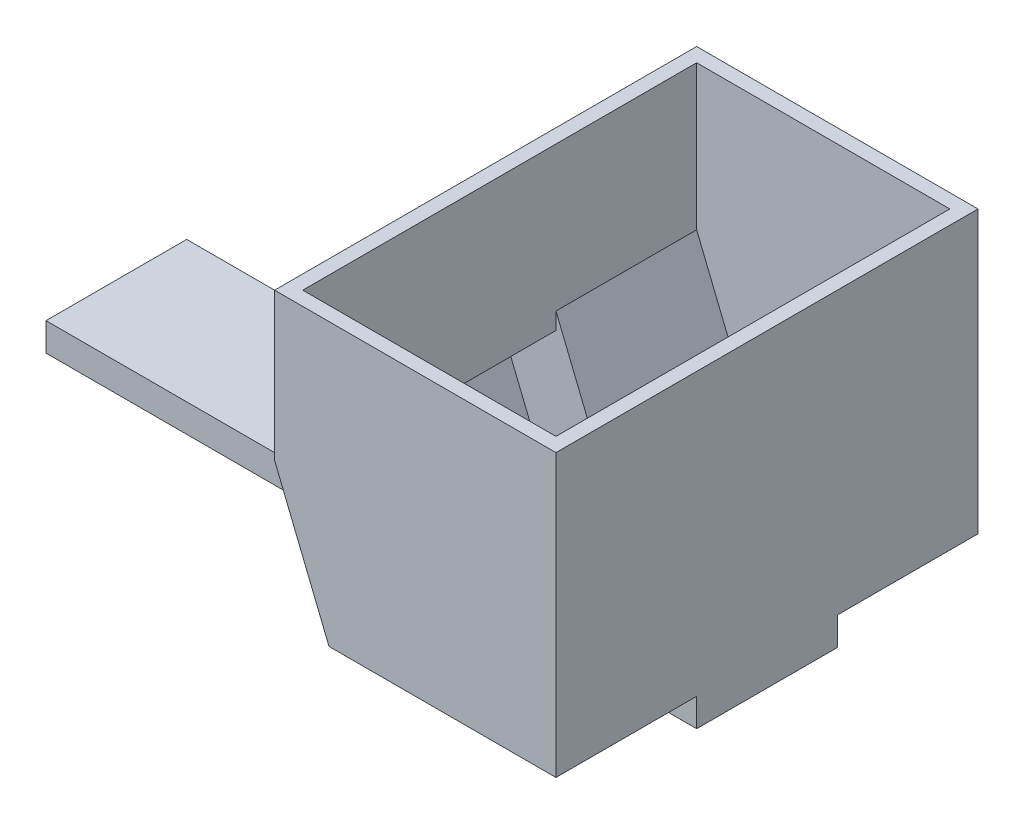
SolidWorks part; units mm, degrees
ref_plane "Front Plane" through (0, 0, 0) normal (0, 0, 1) x (1, 0, 0)
ref_plane "Top Plane" through (0, 0, 0) normal (0, 1, 0) x (1, 0, 0)
ref_plane "Right Plane" through (0, 0, 0) normal (1, 0, 0) x (0, 0, -1)
sketch "Sketch7" plane through (0, 0, 0) normal (0, 0, 1) x (1, 0, 0)
  point P0 (0, 0)
  point P1 (0, 0)
  point P2 (0, 0)
  point P5 (5156.861, -1595.0663)
  point P19 (4895.353, -895.9009)
sketch "Sketch14" plane through (0, 0, 0) normal (0, 0, 1) x (1, 0, 0)
  line L6 (5023.7407, -2387.179) -> (6023.7407, -2387.179)
  point P0 (0, -2787.179)
  point P1 (0, 0)
  line B0 (4250, -482.916) -> (5023.7407, -2387.179)
  line B1 (0, -2387.179) -> (9250, -2387.179)
  line B2 (0, -2387.179) -> (0, -2787.179)
  line B3 (0, -2787.179) -> (9250, -2787.179)
  line B4 (9250, -2387.179) -> (9250, -2787.179)
  line B5 (4250, -482.916) -> (5250, -482.916)
  line B6 (5250, -482.916) -> (6023.7407, -2387.179)
  line B7 (9250, -2387.179) -> (9250, 1612.821)
  line B8 (9250, 1612.821) -> (5250, 1612.821)
  line B9 (5250, 1612.821) -> (5250, -482.916)
  circle B10 centre (4895.353, -895.9009) radius 100
  circle B11 centre (5156.861, -1595.0663) radius 100
sketch_block_instance "Block1-1"
sketch_block "Block1"
extrude "Boss-Extrude1" add sketch "Sketch14" along normal blind 2000 contours B6 B5 B0 B1 B11 B10 | B4 B1 B2 B3 | B10 | B11 region at (5140.6497, -1441.5156, 0) region at (4625, -2587.179, 0) region at (4895.353, -895.9009, 0) region at (5156.861, -1595.0663, 0)
extrude "Boss-Extrude2" add sketch "Sketch14<3>" along normal blind 4000 and the other way blind 2000 contours B8 B9 B6 B1 B7 region at (7334.0841, -321.2836, 0)
sketch "Sketch14<3>" plane through (0, 0, 0) normal (0, 0, 1) x (1, 0, 0) same geometry as "Sketch14"
shell "Shell2" thickness 200 removed face at (7250, 1612.821, 1000)
sketch "Sketch16" plane through (0, 0, 2000) normal (0, 0, 1) x (1, 0, 0)
  circle A1 centre (4895.353, -895.9009) radius 100
  circle A2 centre (4895.353, -895.9009) radius 100 construction
extrude "Boss-Extrude3" add sketch "Sketch16" along normal blind 400
extrude "Boss-Extrude4" add sketch "Sketch14<4>" against normal blind 400 contours B11
sketch "Sketch14<4>" plane through (0, 0, 0) normal (0, 0, 1) x (1, 0, 0) same geometry as "Sketch14"
